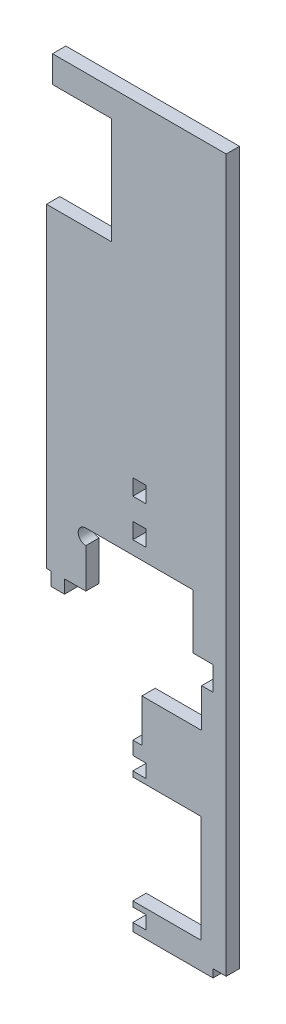
SolidWorks part; units mm, degrees
material "Balsa"
ref_plane "Plan de face" through (0, 0, 0) normal (0, 0, 1) x (1, 0, 0)
ref_plane "Plan de dessus" through (0, 0, 0) normal (0, 1, 0) x (1, 0, 0)
ref_plane "Plan de droite" through (0, 0, 0) normal (1, 0, 0) x (0, 0, -1)
sketch "Esquisse1" plane through (0, 0, 0) normal (0, 0, 1) x (1, 0, 0)
  line L0 (65.1211, 0) -> (30.1224, 0)
  line L2 (65.1211, 0) -> (65.1211, 270)
  line L3 (65.1211, 270) -> (0, 270)
  line L4 (0, 270) -> (0, 260)
  line L5 (0, 260) -> (22.181, 260)
  line L6 (-2.2595, 101.7504) -> (12.493, 101.7504)
  line L7 (12.493, 101.7504) -> (12.493, 122.247)
  line L8 (12.493, 122.247) -> (52.693, 122.247)
  line L9 (52.693, 122.247) -> (52.693, 101.7504)
  line L10 (52.693, 101.7504) -> (55.9116, 101.7504)
  line L11 (1.3186, 101.7504) -> (30.1224, 101.7504) construction
  line L12 (55.9116, 101.7504) -> (55.9116, 78.2407)
  line L13 (55.9116, 78.2407) -> (33.5123, 78.2407)
  line L14 (33.5123, 78.2407) -> (33.5123, 62.2)
  line L15 (33.5123, 62.2) -> (30.1224, 62.2)
  line L16 (30.1224, 62.2) -> (30.1224, 57.2)
  line L17 (30.1224, 50.2) -> (55.6176, 50.2)
  line L18 (30.1224, 57.2) -> (35.1224, 57.2)
  line L19 (22.181, 260) -> (22.181, 220)
  line L20 (35.1224, 57.2) -> (35.1224, 52.2)
  line L21 (22.181, 220) -> (-2.2595, 220)
  line L22 (-2.2595, 220) -> (-2.2595, 101.7504)
  line L23 (35.1224, 52.2) -> (30.1224, 52.2)
  line L24 (30.1224, 52.2) -> (30.1224, 50.2)
  line L25 (30.1224, 0) -> (30.1224, 3)
  line L26 (30.1224, 3) -> (35.1224, 3)
  line L27 (35.1224, 3) -> (35.1224, 8)
  line L30 (35.1224, 8) -> (30.1224, 8)
  line L31 (30.1224, 8) -> (30.1224, 10)
  line L32 (30.1224, 10) -> (55.6176, 10)
  line L33 (55.6176, 10) -> (55.6176, 50.2)
  dimension "D1" = 270
  dimension "D2" = 65.1211
  dimension "D3" = 40.2
  dimension "D4" = 2
  dimension "D5" = 20.4965
  dimension "D6" = 40.2
  dimension "D7" = 40
  dimension "D8" = 10
  dimension "D9" = 12.4281
  dimension "D10" = 25.4952
  dimension "D11" = 5
  dimension "D12" = 5
  dimension "D13" = 5
  dimension "D14" = 2
  dimension "D15" = 5
  dimension "D16" = 5
  dimension "D17" = 25.4952
extrude "Boss.-Extru.1" add sketch "Esquisse1" against normal blind 5
sketch "Esquisse2" plane through (0, 0, 0) normal (0, 0, 1) x (1, 0, 0)
  line L0 (52.693, 101.7504) -> (55.9116, 101.7504) construction
  line L1 (35.1224, 147.4016) -> (30.1224, 147.4016)
  line L2 (12.493, 122.247) -> (52.693, 122.247) construction
  line L3 (12.493, 101.7504) -> (12.493, 122.247) construction
  line L4 (35.1224, 147.4016) -> (35.1224, 141.4016)
  line L5 (35.1224, 141.4016) -> (30.1224, 141.4016)
  line L6 (30.1224, 147.4016) -> (30.1224, 141.4016)
  line L7 (35.1224, 133.247) -> (30.1224, 133.247)
  line L8 (35.1224, 133.247) -> (35.1224, 127.247)
  line L9 (35.1224, 127.247) -> (30.1224, 127.247)
  line L10 (30.1224, 133.247) -> (30.1224, 127.247)
  line L11 (55.9116, 101.7504) -> (60.186, 101.7504)
  line L12 (55.9116, 101.7504) -> (55.9116, 92.7704)
  line L13 (55.9116, 92.7704) -> (60.186, 92.7704)
  line L14 (60.186, 101.7504) -> (60.186, 92.7704)
  line L15 (52.693, 122.247) -> (52.693, 101.7504) construction
  line L16 (65.1211, 0) -> (65.1211, 270) construction
  line L17 (65.1211, 0) -> (60.2011, 0)
  line L18 (65.1211, 0) -> (65.1211, 3)
  line L19 (65.1211, 3) -> (60.2011, 3)
  line L20 (60.2011, 0) -> (60.2011, 3)
  line L21 (30.1224, 0) -> (65.1211, 0) construction
  circle A0 centre (12.493, 119.3895) radius 2.8575
  dimension "D1" = 2.8575
  dimension "D2" = 7.493
  dimension "D3" = 4.92
  dimension "D4" = 3
extrude "Enlèv. mat.-Extru.1" cut sketch "Esquisse2" against normal blind 5
sketch "Esquisse3" plane through (0, 0, 0) normal (0, 0, 1) x (1, 0, 0)
  line L1 (4.493, 101.7504) -> (-0.507, 101.7504)
  line L2 (4.493, 101.7504) -> (4.493, 96.7504)
  line L3 (4.493, 96.7504) -> (-0.507, 96.7504)
  line L4 (-0.507, 101.7504) -> (-0.507, 96.7504)
  line L6 (-2.2595, 101.7504) -> (12.493, 101.7504) construction
  line L7 (12.493, 101.7504) -> (12.493, 116.532) construction
  dimension "D1" = 8
  dimension "D2" = 5
  dimension "D3" = 5
extrude "Boss.-Extru.2" add sketch "Esquisse3" against normal blind 5
